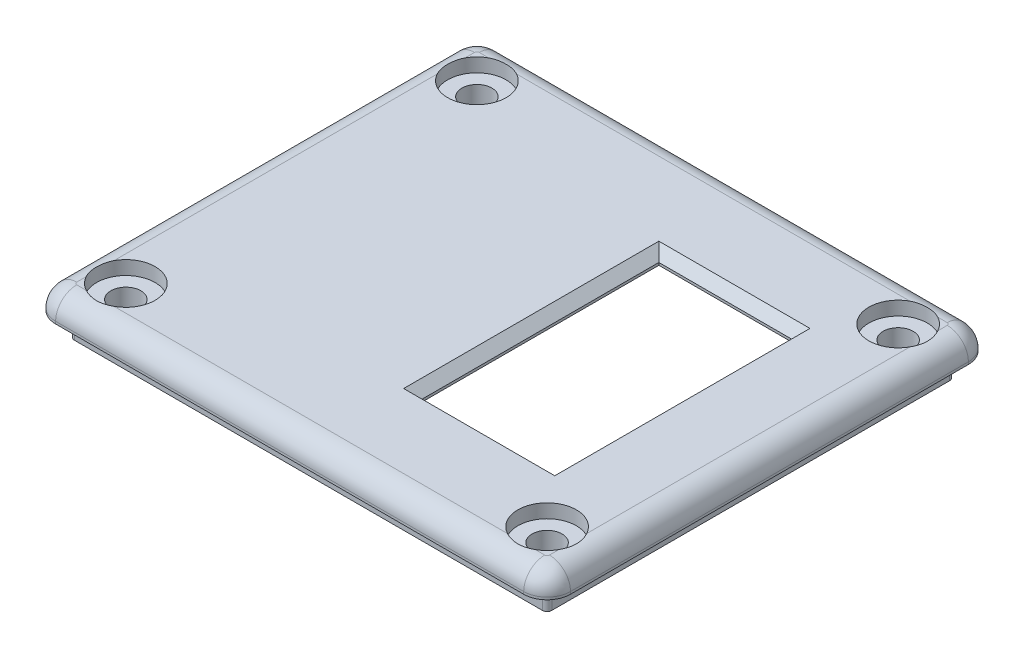
SolidWorks part; units mm, degrees
ref_plane "Front Plane" through (0, 0, 0) normal (0, 0, 1) x (1, 0, 0)
ref_plane "Top Plane" through (0, 0, 0) normal (0, 1, 0) x (1, 0, 0)
ref_plane "Right Plane" through (0, 0, 0) normal (1, 0, 0) x (0, 0, -1)
sketch "Sketch1" plane through (0, 0, 0) normal (0, 1, 0) x (1, 0, 0)
  line L5 (27.305, -22.225) -> (-27.305, 22.225) construction
  line L6 (27.305, 22.225) -> (-27.305, -22.225) construction
  line L10 (24.13, 24.13) -> (-26.67, 24.13)
  line L11 (-29.21, -21.59) -> (-29.21, 21.59)
  line L12 (24.13, -24.13) -> (-26.67, -24.13)
  line L13 (26.67, -21.59) -> (26.67, 21.59)
  arc A4 (-26.67, 24.13) -> (-29.21, 21.59) centre (-26.67, 21.59) ccw
  arc A5 (-29.21, -21.59) -> (-26.67, -24.13) centre (-26.67, -21.59) ccw
  arc A6 (24.13, -24.13) -> (26.67, -21.59) centre (24.13, -21.59) ccw
  arc A7 (26.67, 21.59) -> (24.13, 24.13) centre (24.13, 21.59) ccw
  point P0 (0, 0)
  dimension "D1" = 55.88
  dimension "D2" = 48.26
extrude "Boss-Extrude1" add sketch "Sketch1" along normal blind 2.54
ref_plane "Plane1" through (-1.27, 0, 0) normal (-1, 0, 0) x (0, 0, 1)
ref_plane "Plane2" through (0, 0, 0) normal (0, 0, 1) x (1, 0, 0)
sketch "Sketch3" plane through (0, 0, 0) normal (0, -1, 0) x (1, 0, 0)
  line L0 (1.397, 0) -> (-1.397, 0) construction
  line L1 (-20.8813, -20.193) -> (18.3413, -20.193)
  line L2 (-25.273, -15.8013) -> (-25.273, 15.8013)
  line L3 (-20.8813, 20.193) -> (18.3413, 20.193)
  line L8 (24.638, -21.59) -> (24.638, 21.59)
  line L9 (24.13, 22.098) -> (-26.67, 22.098)
  line L10 (-27.178, 21.59) -> (-27.178, -21.59)
  line L11 (-26.67, -22.098) -> (24.13, -22.098)
  line L12 (24.638, -21.59) -> (24.638, 21.59)
  line L13 (24.13, 22.098) -> (-26.67, 22.098)
  line L14 (-27.178, 21.59) -> (-27.178, -21.59)
  line L15 (-26.67, -22.098) -> (24.13, -22.098)
  line L16 (22.733, -15.8013) -> (22.733, 15.8013)
  line L17 (-24.638, -19.558) -> (22.098, 19.558) construction
  line L18 (-24.638, 19.558) -> (22.098, -19.558) construction
  line L19 (-1.27, 1.397) -> (-1.27, -1.397) construction
  arc A0 (22.733, 15.8013) -> (18.3413, 20.193) centre (22.098, 19.558) cw
  arc A1 (22.733, -15.8013) -> (18.3413, -20.193) centre (22.098, -19.558) ccw
  arc A2 (-25.273, -15.8013) -> (-20.8813, -20.193) centre (-24.638, -19.558) cw
  arc A3 (-20.8813, 20.193) -> (-25.273, 15.8013) centre (-24.638, 19.558) cw
  arc A8 (24.13, -22.098) -> (24.638, -21.59) centre (24.13, -21.59) ccw
  arc A9 (24.638, 21.59) -> (24.13, 22.098) centre (24.13, 21.59) ccw
  arc A10 (-26.67, 22.098) -> (-27.178, 21.59) centre (-26.67, 21.59) ccw
  arc A11 (-27.178, -21.59) -> (-26.67, -22.098) centre (-26.67, -21.59) ccw
  arc A12 (24.13, -22.098) -> (24.638, -21.59) centre (24.13, -21.59) ccw
  arc A13 (24.638, 21.59) -> (24.13, 22.098) centre (24.13, 21.59) ccw
  arc A14 (-26.67, 22.098) -> (-27.178, 21.59) centre (-26.67, 21.59) ccw
  arc A15 (-27.178, -21.59) -> (-26.67, -22.098) centre (-26.67, -21.59) ccw
  point P0 (-1.27, 0)
  dimension "D4" = 3.81
  dimension "D3" = 1.905
  dimension "D2" = 1.905
  dimension "D5" = 1.905
  dimension "D6" = 1.905
  dimension "D1" = 2.032
extrude "Boss-Extrude2" add sketch "Sketch3" along normal blind 2.54
fillet "Fillet1" radius 2.286 8 edges at (-1.27, 2.54, -24.13) (25.9261, 2.54, -23.3861) (26.67, 2.54, 0) (25.9261, 2.54, 23.3861) (-1.27, 2.54, 24.13) (-28.4661, 2.54, 23.3861) (-29.21, 2.54, 0) (-28.4661, 2.54, -23.3861)
hole_wizard "CBORE for #4 Button Head Cap Screw" positions "Sketch4" profile "Sketch5" counterbore size "#4" standard "ANSI Inch" end condition through all
sketch "Sketch4" plane through (107.3253, 2.54, -177.8827) normal (0, 1, 0) x (1, 0, 0)
  point P0 (-85.7353, -158.8327)
  point P3 (-85.7353, -196.9327)
  point P6 (-131.4553, -158.8327)
  point P9 (-131.4553, -196.9327)
sketch "Sketch5" plane through (21.59, 2.54, -19.05) normal (1, 0, 0) x (0, 0, 1)
  line L0 (0, 0) -> (0, 5.08)
  line L1 (0, 5.08) -> (1.632, 5.08)
  line L2 (1.632, 5.08) -> (1.632, 1.4986)
  line L3 (1.632, 1.4986) -> (3.175, 1.4986)
  line L4 (3.175, 1.4986) -> (3.175, 0)
  line L5 (3.175, 0) -> (0, 0)
  line L6 (0, -6.35) -> (0, 107.95) construction
  dimension "Thru Hole Dia." = 3.2639
  dimension "Thru Hole Depth" = 5.08
  dimension "C'Bore Dia." = 6.35
  dimension "C'Bore Depth" = 1.4986
extrude "Cut-Extrude1" cut sketch "Sketch6" against normal through all
sketch "Sketch6" plane through (107.3253, 2.54, -177.8827) normal (0, 1, 0) x (-1, 0, 0)
  line L1 (91.1063, 165.0327) -> (105.5063, 165.0327)
  line L2 (91.1063, 165.0327) -> (91.1063, 190.7327)
  line L3 (91.1063, 190.7327) -> (105.5063, 190.7327)
  line L4 (105.5063, 165.0327) -> (105.5063, 190.7327)
sketch "Sketch7" plane through (0, 0, 0) normal (0, -1, 0) x (1, 0, 0)
  line L34 (-0.7209, -15.39) -> (18.7591, -15.39)
  line L35 (18.7591, -15.39) -> (18.7591, 15.39)
  line L36 (18.7591, 15.39) -> (-0.7209, 15.39)
  line L37 (-0.7209, 15.39) -> (-0.7209, -15.39)
  line L38 (-0.7209, -15.39) -> (18.7591, -15.39)
  line L39 (18.7591, -15.39) -> (18.7591, 15.39)
  line L40 (18.7591, 15.39) -> (-0.7209, 15.39)
  line L41 (-0.7209, 15.39) -> (-0.7209, -15.39)
  dimension "D1" = 2.54
extrude "Cut-Extrude2" cut sketch "Sketch7" against normal blind 1.27
chamfer "Chamfer1" distance 1 angle 45 4 edges at (9.0191, 2.54, 12.85) (16.2191, 2.54, 0) (1.8191, 2.54, 0) (9.0191, 2.54, -12.85)
hole_wizard "#4-40 Tapped Hole1" positions "Sketch8" profile "Sketch9" tap size "#4-40" standard "ANSI Inch"
sketch "Sketch8" plane through (107.3253, 0, -177.8827) normal (0, -1, 0) x (-1, 0, 0)
  point P0 (88.4863, -189.5327)
  point P3 (88.4863, -166.2327)
  point P6 (112.2863, -166.2327)
  point P9 (112.2863, -189.5327)
sketch "Sketch9" plane through (18.8391, 0, 11.65) normal (1, 0, 0) x (0, 0, -1)
  line L0 (0, 0) -> (0, 1.9492)
  line L1 (0, 1.9492) -> (1.1303, 1.27)
  line L2 (1.1303, 1.27) -> (1.1303, 0)
  line L3 (1.1303, 0) -> (0, 0)
  line L4 (0, 1.9492) -> (-1.1303, 1.27) construction
  line L5 (0, -6.35) -> (0, 107.95) construction
  dimension "Tap Drill Dia." = 2.2606
  dimension "Tap Drill Depth" = 1.27
  dimension "Drill Angle" = 118
cosmetic thread "Hole Thread1" parameters "D1"=1.27, "D2"=2.8448
cosmetic thread "Hole Thread2" parameters "D1"=1.27, "D2"=2.8448
cosmetic thread "Hole Thread3" parameters "D1"=1.27, "D2"=2.8448
cosmetic thread "Hole Thread4" parameters "D1"=1.27, "D2"=2.8448
sketch "Sketch10" plane through (0, 0, 0) normal (0, -1, 0) x (1, 0, 0)
  circle A0 centre (18.8391, 11.65) radius 1.85
  circle A1 centre (18.8391, -11.65) radius 1.85
  circle A2 centre (-4.9609, -11.65) radius 1.85
  circle A3 centre (-4.9609, 11.65) radius 1.85
  circle A4 centre (18.8391, -11.65) radius 1.1303
  circle A5 centre (18.8391, 11.65) radius 1.1303
  circle A6 centre (-4.9609, 11.65) radius 1.1303
  circle A7 centre (-4.9609, -11.65) radius 1.1303
  dimension "D1" = 3.7
extrude "Boss-Extrude3" add sketch "Sketch10" along normal blind 1.397 and the other way up to surface (1.27 mm away) other way up to face at (13.6265, 1.27, 0)
chamfer "Chamfer2" distance 1 angle 45 4 edges at (20.6891, 0, -11.65) (20.6891, 0, 11.65) (-4.9609, 0, 13.5) (-4.9609, 0, -9.8)
